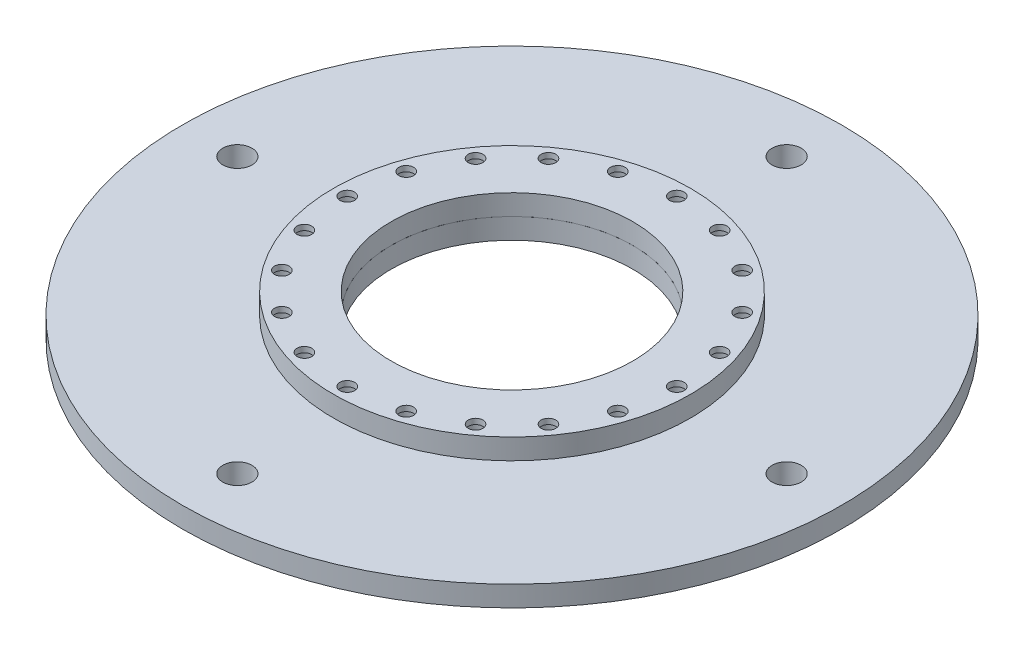
SolidWorks part; units mm, degrees
ref_plane "Front Plane" through (0, 0, 0) normal (0, 0, 1) x (1, 0, 0)
ref_plane "Top Plane" through (0, 0, 0) normal (0, 1, 0) x (1, 0, 0)
ref_plane "Right Plane" through (0, 0, 0) normal (1, 0, 0) x (0, 0, -1)
sketch "Sketch9" plane through (0, 0, 0) normal (0, 1, 0) x (1, 0, 0)
  circle A2 centre (0, 0) radius 82.55
  circle A4 centre (0, 0) radius 55.88
  circle A5 centre (0, 0) radius 76.2 construction
  point P6 (0, 76.2)
  point P34 (0, 0)
  dimension "Diameter_BackPlate" = 165.1
  dimension "Diameter_FuelOuterPlenum" = 111.76
  dimension "Diameter_BackPlate_BoltCircle" = 152.4
extrude "REF_BackPlate" add sketch "Sketch9" along normal blind 9.525 contours A2 A4 region at (-80.2151, 0, 0)
sketch "Sketch1" plane through (0, 0, 0) normal (0, 1, 0) x (1, 0, 0)
  line L1 (0, 82.55) -> (0, 81.788) construction
  line L2 (0, 81.788) -> (0, 76.2) construction
  line L6 (8.7416, 55.192) -> (11.0014, 69.4604) construction
  line L7 (0, 82.55) -> (0, 127) construction
  line L8 (39.2452, 120.7842) -> (25.5094, 78.5097) construction
  line L9 (8.7416, 55.192) -> (0, 0) construction
  circle A3 centre (0, 0) radius 152.4
  circle A8 centre (0, 0) radius 127 construction
  circle A14 centre (0, 76.2) radius 5.588 construction
  circle A15 centre (0, 0) radius 55.88 construction
  circle A17 centre (0, 0) radius 82.55 construction
  circle A18 centre (23.5471, 72.4705) radius 5.588 construction
  circle A19 centre (0, 0) radius 76.2 construction
  circle A20 centre (0, 0) radius 55.88
  circle A23 centre (0, 0) radius 70.3262 construction
  arc A24 (0, 76.2) -> (23.5471, 72.4705) centre (0, 0) cw construction
  point P2 (0, 127)
  point P5 (0, 70.3262)
  point P12 (11.9203, 75.2619)
  point P22 (0, 0)
  point P23 (11.0014, 69.4604)
  point P24 (11.0014, 69.4604)
  point P25 (0, 0)
  point P27 (0, 0)
  point P31 (0, 0)
  point P34 (0, 66.8825)
  point P35 (1.9168, 70.3001)
  point P36 (9.8116, 61.9478)
  dimension "Diameter_Takeout_BoltCircle" = 254
  dimension "Diameter_ThrustPlate" = 304.8
  dimension "D1" = 11.176
  dimension "D2" = 140.6525
  dimension "D3" = 18
sketch "Sketch20" plane through (0, 0, 0) normal (0, -1, 0) x (-1, 0, 0)
  point P0 (0, 76.2)
hole_wizard "REF_CBORE_BackPlate" positions "Sketch20" profile "Sketch21" counterbore size "1/4" standard "ANSI Inch" end condition through all
sketch "Sketch21" plane through (0, 0, -76.2) normal (1, 0, 0) x (0, 0, -1)
  line L0 (0, 0) -> (0, 9.525)
  line L1 (0, 9.525) -> (3.3782, 9.525)
  line L3 (3.3782, 9.525) -> (3.3782, 6.985)
  line L4 (3.3782, 6.985) -> (5.588, 6.985)
  line L5 (5.588, 6.985) -> (5.588, 0)
  line L7 (5.588, 0) -> (0, 0)
  line L11 (0, -6.35) -> (0, 107.95) construction
  dimension "Thru Hole Dia." = 6.7564
  dimension "Thru Hole Depth" = 9.525
  dimension "C'Bore Dia." = 11.176
  dimension "C'Bore Depth" = 6.985
pattern_circular "REF_CBORE_BackPlate_Pattern" count 20 over 360 about axis through (0, 9.525, 0) along (0, -1, 0) of "REF_CBORE_BackPlate"
extrude "ThrustPlate_TC3" add sketch "Sketch1" against normal blind 9.525 separate body contours A3 region at (-148.0895, 0, 0)
sketch "Sketch11" plane through (0, 0, 0) normal (0, 1, 0) x (1, 0, 0)
  point P0 (0, 127)
hole_wizard "UNDEF_Clearance_ThrustPlate" positions "Sketch11" profile "Sketch12" hole size "1/2" standard "ANSI Inch" end condition through all
sketch "Sketch12" plane through (0, 0, -127) normal (1, 0, 0) x (0, 0, 1)
  line L0 (0, 0) -> (0, 9.525)
  line L1 (0, 9.525) -> (6.7462, 9.525)
  line L2 (6.7462, 9.525) -> (6.7462, 0)
  line L5 (6.7462, 0) -> (0, 0)
  line L11 (0, -6.35) -> (0, 107.95) construction
  dimension "Thru Hole Dia." = 13.4925
  dimension "Thru Hole Depth" = 9.525
pattern_circular "Clearance_ThrustPlate_Pattern" count 4 over 360 about axis through (0, -9.525, 0) along (0, 1, 0) of "UNDEF_Clearance_ThrustPlate" reverse direction yes
sketch "Sketch22" plane through (0, 0, 0) normal (0, 1, 0) x (1, 0, 0)
  point P0 (0, 70.3262)
hole_wizard "#10 Clearance Hole1" positions "Sketch22" profile "Sketch23" hole size "#10" standard "ANSI Inch" end condition through all
sketch "Sketch23" plane through (0, 0, -70.3262) normal (1, 0, 0) x (0, 0, 1)
  line L0 (0, 0) -> (0, 9.525)
  line L1 (0, 9.525) -> (2.5527, 9.525)
  line L2 (2.5527, 9.525) -> (2.5527, 0)
  line L5 (2.5527, 0) -> (0, 0)
  line L11 (0, -6.35) -> (0, 107.95) construction
  dimension "Thru Hole Dia." = 5.1054
  dimension "Thru Hole Depth" = 9.525
pattern_circular "CirPattern1" count 10 over 360 about axis through (0, -9.525, 0) along (0, 1, 0) of "#10 Clearance Hole1" reverse direction yes
equation "\"Diameter_BackPlate\"= 6.5"
equation "\"VAR_Diameter_BackPlate_BoltCircle\"= 6"
equation "\"VAR_Diameter_FuelOuterPlenum\"= 4.4"
equation "\"Diameter_BackPlate@Sketch9\"=\"Diameter_BackPlate\""
equation "\"Diameter_BackPlate_BoltCircle@Sketch9\"=\"VAR_Diameter_BackPlate_BoltCircle\""
equation "\"Diameter_FuelOuterPlenum@Sketch9\"=\"VAR_Diameter_FuelOuterPlenum\""
equation "\"Thickness_ThrustPlate\"= 0.375'undetermined"
equation "\"Diameter_ThrustPlate\"= 12'defined"
equation "\"Diameter_Takeout_BoltCicle\"= 10'defined"
equation "\"Diameter_Takeout_BoltCircle@Sketch1\"=\"Diameter_Takeout_BoltCicle\""
equation "\"Diameter_ThrustPlate@Sketch1\"=\"Diameter_ThrustPlate\""
equation "\"D1@ThrustPlate_TC3\"=\"Thickness_ThrustPlate\""
equation "\"VAR_Diameter_CBORE\"= 0.44'undetermined"
equation "\"VAR_Diameter_Clearance_ThrustPlate\"= 0.25'undetermined"
equation "\"D3@Sketch1\"=360/\"D1@REF_CBORE_BackPlate_Pattern\""
equation "\"D1@Sketch1\"=\"C'Bore Dia.@Sketch21\"''''''''''''''''''''''''''''''''''''''"
equation "\"C'Bore Dia.@Sketch21\"=\"VAR_Diameter_CBORE\""
equation "\"NumberBolts_BackPlate\"= 20"
equation "\"NumberBolts_Takeout\"= 4'defined"
equation "\"D1@Clearance_ThrustPlate_Pattern\"=\"NumberBolts_Takeout\""
equation "\"D1@REF_CBORE_BackPlate_Pattern\"=\"NumberBolts_BackPlate\""
